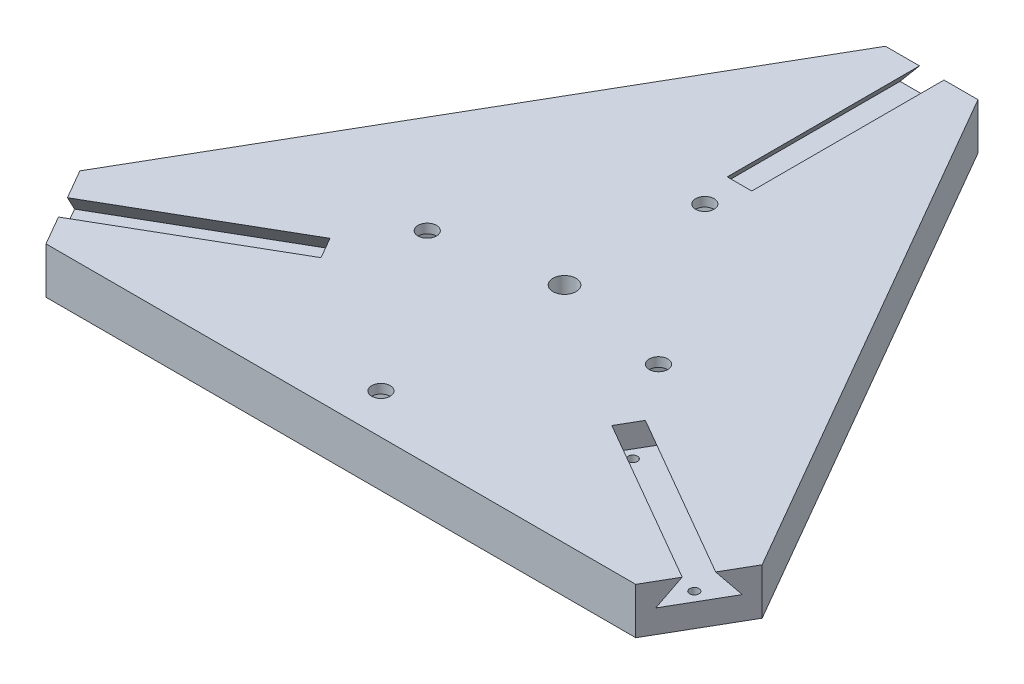
SolidWorks part; units mm, degrees
material "PLA"
ref_plane "Plan de face" through (0, 0, 0) normal (0, 0, 1) x (1, 0, 0)
ref_plane "Plan de dessus" through (0, 0, 0) normal (0, 1, 0) x (1, 0, 0)
ref_plane "Plan de droite" through (0, 0, 0) normal (1, 0, 0) x (0, 0, -1)
sketch "Esquisse1" plane through (0, 0, 0) normal (0, 1, 0) x (1, 0, 0)
  line L29 (-10, 79.3725) -> (10, 79.3725)
  line L30 (73.7386, -31.026) -> (63.7386, -48.3465)
  line L31 (-63.7386, -48.3465) -> (-73.7386, -31.026)
  line L32 (-10, 79.3725) -> (-73.7386, -31.026)
  line L33 (-63.7386, -48.3465) -> (63.7386, -48.3465)
  line L34 (73.7386, -31.026) -> (10, 79.3725)
  circle A7 centre (0, 0) radius 2.5
  circle A8 centre (0, 0) radius 79.3725 construction
  point P17 (0, 0)
  dimension "D1" = 20
  dimension "D4" = 20
  dimension "D5" = 80
  dimension "D6" = 80
  dimension "D3" = 80
  dimension "D9" = 5
  dimension "D12" = 79.3725
  dimension "D2" = 20
  dimension "D7" = 60
  dimension "D8" = 60
  dimension "D10" = 80
  dimension "D11" = 80
extrude "Boss.-Extru.1" add sketch "Esquisse1" along normal mid plane 10
sketch "Esquisse2" plane through (0, 5, 0) normal (0, 1, 0) x (1, 0, 0)
  line L0 (-68.7386, -39.6863) -> (0, 0) construction
  line L1 (-73.7386, -31.026) -> (-63.7386, -48.3465) construction
  circle A0 centre (-66.3571, -38.3113) radius 1
  circle A1 centre (-34.9203, -20.1613) radius 1
  dimension "D1" = 2
  dimension "D4" = 2
  dimension "D2" = 2.75
  dimension "D3" = 39.05
extrude "Enlèv. mat.-Extru.1" cut sketch "Esquisse2" against normal through all
pattern_circular "Répétition circulaire1" count 3 over 360 about axis through (0, 5, 0) along (0, -1, 0) of "Enlèv. mat.-Extru.1" reverse direction yes
sketch "Esquisse3" plane through (68.7386, 0, 39.6863) normal (0.866, 0, 0.5) x (0.5, 0, -0.866)
  line L0 (2.65, 5) -> (6.845, 0)
  line L1 (-10, 5) -> (10, 5) construction
  line L3 (-6.845, 0) -> (-2.65, 5)
  line L4 (-2.65, 5) -> (2.65, 5)
  line L6 (-6.845, 0) -> (6.845, 0)
  point P6 (0, 5)
  point P11 (0, 0)
  dimension "D1" = 5.3
  dimension "D2" = 13.69
extrude "Enlèv. mat.-Extru.2" cut sketch "Esquisse3" against normal blind 41.553
pattern_circular "Répétition circulaire2" count 3 over 360 about axis through (0, 5, 0) along (0, -1, 0) of "Enlèv. mat.-Extru.2"
sketch "Esquisse4" plane through (0, -5, 0) normal (0, -1, 0) x (1, 0, 0)
  line L0 (0, 0) -> (25, 0) construction
  line L1 (25, 0) -> (25, 4.68) construction
  line L2 (0, 0) -> (-25, 0) construction
  line L3 (-25, 0) -> (-25, 4.68) construction
  circle A3 centre (0, -30.3225) radius 2
  circle A4 centre (0, -40.3225) radius 1 construction
  circle A7 centre (0, 39.68) radius 2
  circle A8 centre (25, 4.68) radius 2
  circle A9 centre (-25, 4.68) radius 2
  point P7 (0, 0)
  point P15 (0, 0)
  dimension "D3" = 25
  dimension "D4" = 4.68
  dimension "D7" = 4
  dimension "D8" = 39.68
  dimension "D1" = 10
  dimension "D2" = 4
  dimension "D5" = 25
  dimension "D9" = 4
  dimension "D10" = 4
  dimension "D6" = 4.68
extrude "Enlèv. mat.-Extru.3" cut sketch "Esquisse4" against normal through all
sketch "Esquisse5" plane through (0, -5, 0) normal (0, -1, 0) x (1, 0, 0)
  line L0 (-19.85, 34.53) -> (19.85, 34.53)
  line L1 (-19.85, 34.53) -> (-19.85, -25.1725)
  line L2 (-19.85, -25.1725) -> (19.85, -25.1725)
  line L3 (19.85, -25.1725) -> (19.85, 34.53)
  line L4 (-30.15, 44.83) -> (30.15, 44.83)
  line L5 (30.15, -35.4725) -> (30.15, 44.83)
  line L6 (-30.15, -35.4725) -> (30.15, -35.4725)
  line L7 (-30.15, 44.83) -> (-30.15, -35.4725)
  circle A0 centre (25, 4.68) radius 2 construction
  circle A1 centre (-25, 4.68) radius 2 construction
  circle A2 centre (0, 39.68) radius 2 construction
  circle A3 centre (0, -30.3225) radius 2 construction
  dimension "D1" = 5.15
  dimension "D2" = 5.15
  dimension "D3" = 5.15
  dimension "D4" = 5.15
  dimension "D5" = 10.3
extrude "Enlèv. mat.-Extru.4" cut sketch "Esquisse5" against normal blind 8
sketch "Esquisse6" plane through (0, -5, 0) normal (0, -1, 0) x (1, 0, 0)
  line L4 (19.85, 34.53) -> (-19.85, 34.53) construction
  circle A0 centre (0, 20.18) radius 3.325
  circle A1 centre (0, 20.18) radius 6.325
  point P4 (0, 0)
  dimension "D2" = 6.65
  dimension "D3" = 3
  dimension "D1" = 14.35
extrude "Boss.-Extru.2" add sketch "Esquisse6" along normal blind 10
